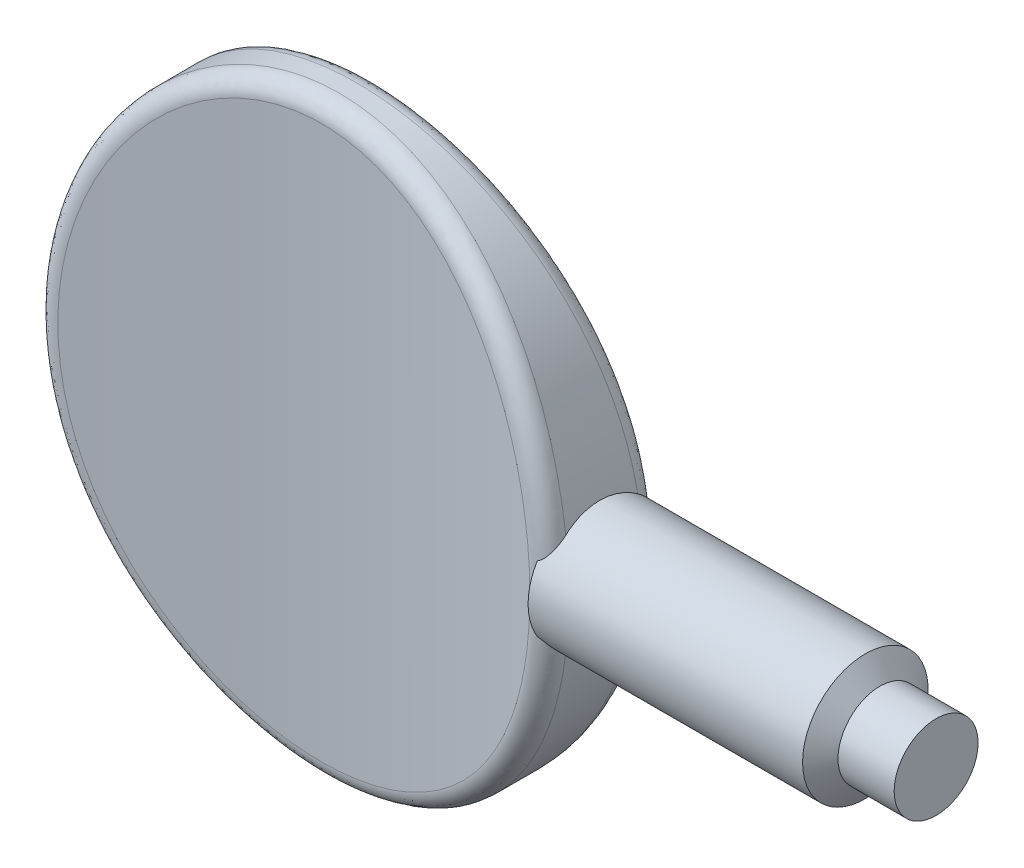
SolidWorks part; units mm, degrees
ref_plane "Front" through (0, 0, 0) normal (0, 0, 1) x (1, 0, 0)
ref_plane "Top" through (0, 0, 0) normal (0, 1, 0) x (1, 0, 0)
ref_plane "Right" through (0, 0, 0) normal (1, 0, 0) x (0, 0, -1)
ref_axis "Axis1" through (-50, 0, 0) along (1, 0, 0)
sketch "Sketch1" plane through (0, 0, 0) normal (0, 0, 1) x (1, 0, 0)
  line L0 (0, 0) -> (22.606, 0) construction
  line L1 (13.208, -2.413) -> (13.208, 2.413)
  line L2 (13.208, -2.413) -> (9.6776, -2.413) construction
  ellipse E0 centre (0, 0) end of major axis (0, -11.303) minor radius 9.906
  dimension "D2" = 3.302
  dimension "B" = 19.812
  dimension "L" = 12.7
extrude "Extrude1" add sketch "Sketch1" along normal mid plane 4.572
sketch "Sketch2" plane through (0, 0, 0) normal (0, 1, 0) x (1, 0, 0)
  line L0 (9.906, 2.286) -> (-9.906, 2.286) construction
  line L1 (0, 0) -> (0, 1.1721) construction
  line L2 (-1.7991, 0) -> (2.0444, 0) construction
  line L3 (-9.906, -2.286) -> (9.906, -2.286) construction
  line L6 (-9.906, 2.286) -> (-9.906, -2.286)
  line L7 (9.906, 2.286) -> (9.906, -2.286)
  arc A0 (-9.906, 2.286) -> (9.906, 2.286) centre (0, 40.2844) ccw
  arc A1 (-9.906, -2.286) -> (9.906, -2.286) centre (0, -40.2844) cw
extrude "Cut-Extrude1" cut sketch "Sketch2" against normal through all and the other way through all flip side to cut
fillet "Fillet3" radius 0.6773 2 edges at (-9.9037, -0.2444, 2.2854) (0.1692, 11.3014, -1.0164)
sketch "Sketch3" plane through (0, 0, 0) normal (0, 1, 0) x (1, 0, 0)
  line L0 (22.606, 0) -> (22.606, 1.6129)
  line L1 (0, 0) -> (17.8703, 0) construction
  line L2 (0, 0) -> (22.606, 0) construction
  line L3 (13.208, 2.413) -> (13.208, 0) construction
  line L4 (13.208, 2.413) -> (19.8868, 2.413)
  line L5 (22.606, 1.6129) -> (20.447, 1.6129)
  line L6 (13.208, 2.413) -> (9.3367, 2.413)
  line L7 (9.0722, 2.0783) -> (9.0722, 0)
  line L8 (9.3367, 0) -> (9.3367, 2.413) construction
  line L9 (9.0722, 0) -> (22.606, 0)
  line L10 (20.447, 1.6129) -> (19.8868, 2.413)
  arc A0 (9.3367, 2.413) -> (9.0722, 2.0783) centre (8.9927, 2.413) cw
  arc A3 (-9.906, 2.286) -> (9.906, 2.286) centre (0, 40.2844) ccw construction
  dimension "D1" = 35
revolve "Revolve1" add sketch "Sketch3" angle 360 about L0
cosmetic thread "Cosmetic Thread1" [suppressed]
sketch "Sketch4" plane through (0, 0, 0) normal (0, 0, 1) x (1, 0, 0)
  line L0 (0, 0) -> (27.7993, 0) construction
  line L1 (19.7035, 2.413) -> (19.8868, 2.0955)
  line L2 (19.8868, 2.0955) -> (20.0701, 2.413)
  line L3 (20.0701, 2.413) -> (20.0701, 2.7796)
  line L4 (20.0701, 2.7796) -> (19.7035, 2.7796)
  line L5 (19.7035, 2.7796) -> (19.7035, 2.413)
  line L6 (19.8868, 2.413) -> (19.8868, -2.413) construction
  dimension "D1" = 4.191
  dimension "D2" = 4.826
revolve "Cut-Revolve10" [suppressed] cut sketch "Sketch4" angle 360 about L0
pattern_linear "LPattern10" [suppressed] count 19 along (-1, 0, 0) of bodies 109
equation "\"D2@Sketch1\" = \"B@Sketch1\" / 6"
equation "\"D1@Fillet3\" = \"C1@Sketch2\" / 3"
equation "\"DIA@Sketch3\" = \"D@Sketch1\""
equation "\"D1@Cosmetic Thread1\" = \"L@Sketch1\" - \"Q@Sketch3\" -  ( \"D@Sketch1\" - \"P@Sketch3\" )  / 1.733"
equation "\"D1@Sketch4\" = \"D2@Cosmetic Thread1\""
equation "\"D2@Sketch4\" = \"DIA@Sketch3\""
equation "\"D1@LPattern10\" = \"D1@Cosmetic Thread1\" / \"P@LPattern10\" "
